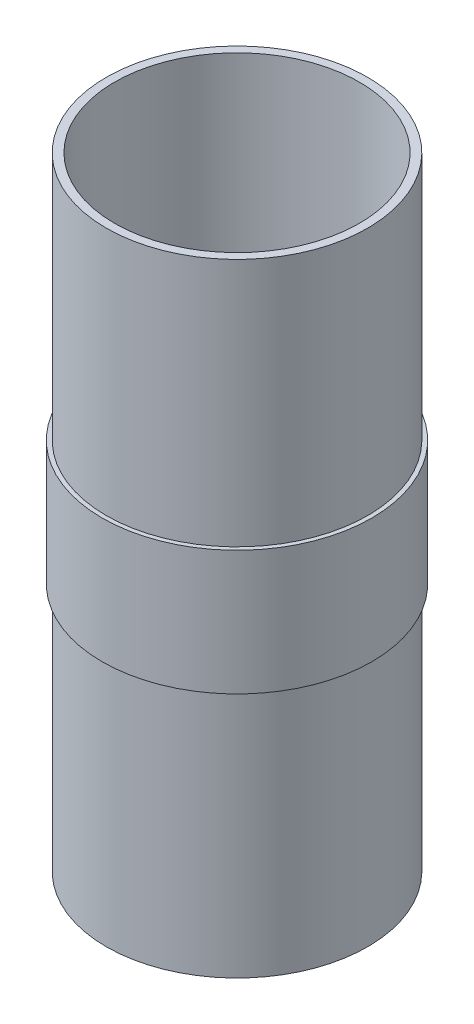
SolidWorks part; units mm, degrees
other "Marcação1"
sketch "Esboço5" plane through (-34.5, 110, -34.5) normal (-0.0418, 0.9983, -0.0408) x (0.9924, 0.0462, 0.1144)
material "Plástico personalizado (1)"
ref_plane "Plano frontal" through (0, 0, 0) normal (0, 0, 1) x (1, 0, 0)
ref_plane "Plano superior" through (0, 0, 0) normal (0, 1, 0) x (1, 0, 0)
ref_plane "Plano direito" through (0, 0, 0) normal (1, 0, 0) x (0, 0, -1)
sketch "Esboço1" plane through (0, 0, 0) normal (0, 1, 0) x (1, 0, 0)
  circle A0 centre (0, 0) radius 31.5
  circle A1 centre (0, 0) radius 29.5
extrude "Ressalto-extrusão1" add sketch "Esboço1" along normal blind 60 contours A1 | A0
sketch "Esboço2" plane through (0, 60, 0) normal (0, 1, 0) x (1, 0, 0)
  circle A0 centre (0, 0) radius 32.5
  circle A1 centre (0, 0) radius 29.5
extrude "Ressalto-extrusão2" add sketch "Esboço2" along normal blind 30 separate body contours A1 | A0
sketch "Esboço3" plane through (0, 90, 0) normal (0, 1, 0) x (1, 0, 0)
  circle A0 centre (0, 0) radius 29.5
  circle A1 centre (0, 0) radius 31.5
extrude "Ressalto-extrusão3" add sketch "Esboço3" along normal blind 60 separate body contours A1 | A0
sketch "Esboço6" plane through (0, 90, 0) normal (0, 1, 0) x (1, 0, 0)
  circle A0 centre (0, 0) radius 30.5
extrude "Ressalto-extrusão4" add sketch "Esboço6" against normal blind 5
combine bodies "Combinar3" operation type add bodies to combine 101 115
